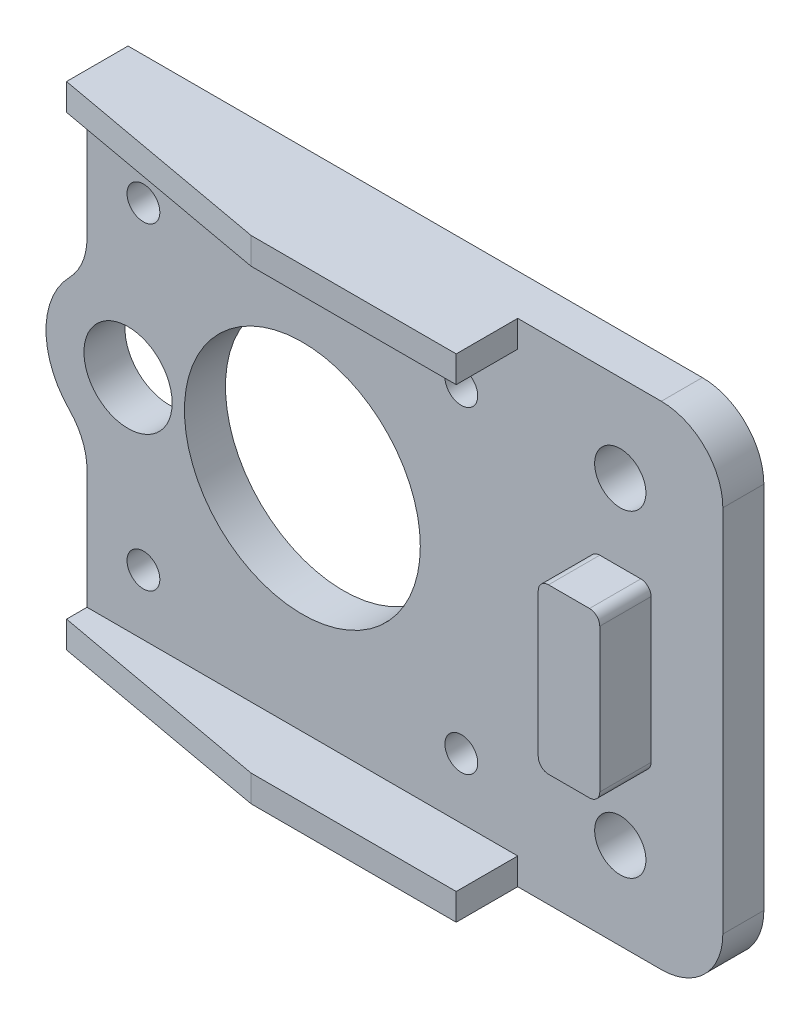
SolidWorks part; units mm, degrees
ref_plane "前视基准面" through (0, 0, 0) normal (0, 0, 1) x (1, 0, 0)
ref_plane "上视基准面" through (0, 0, 0) normal (0, 1, 0) x (1, 0, 0)
ref_plane "右视基准面" through (0, 0, 0) normal (1, 0, 0) x (0, 0, -1)
sketch "草图1" plane through (0, 0, 0) normal (0, 0, 1) x (1, 0, 0)
  line L0 (-21, 6.9282) -> (-21, 24) construction
  line L1 (-21, -24) -> (21, -24) construction
  line L2 (-21, -24) -> (-21, -6.9282) construction
  line L3 (-21, 24) -> (21, 24) construction
  line L4 (21, -24) -> (21, 24) construction
  line L5 (-21, -24) -> (21, 24) construction
  line L6 (-21, 24) -> (21, -24) construction
  line L7 (-21, 24) -> (35, 24)
  line L8 (-21, 24) -> (-21, 9.798)
  line L9 (-21, -24) -> (35, -24)
  line L10 (41, 18) -> (41, -18)
  line L11 (-21, -9.798) -> (-21, -24)
  line L12 (-1000, 0) -> (49000, 0) construction
  circle A0 centre (0, 0) radius 11.5
  circle A1 centre (15.5, 15.5) radius 1.6
  circle A2 centre (15.5, -15.5) radius 1.6
  circle A3 centre (-15.5, -15.5) radius 1.6
  circle A4 centre (-15.5, 15.5) radius 1.6
  circle A5 centre (-17, 0) radius 4.3
  arc A6 (-22.7143, 5.5988) -> (-22.7143, -5.5988) centre (-17, 0) ccw
  arc A7 (35, -24) -> (41, -18) centre (35, -18) ccw
  arc A8 (35, 24) -> (41, 18) centre (35, 18) cw
  arc A9 (-21, -9.798) -> (-22.7143, -5.5988) centre (-27, -9.798) ccw
  arc A10 (-21, 9.798) -> (-22.7143, 5.5988) centre (-27, 9.798) cw
  circle A11 centre (31, 15.5) radius 2.5
  circle A12 centre (31, -15.5) radius 2.5
  point P0 (0, 0)
  point P21 (0, 0)
  dimension "D4" = 23
  dimension "D7" = 3.2
  dimension "D9" = 8.6
  dimension "D11" = 8
  dimension "D12" = 6
  dimension "D13" = 5
  dimension "D1" = 48
  dimension "D2" = 42
  dimension "D3" = 20
  dimension "D5" = 15.5
  dimension "D6" = 15.5
  dimension "D10" = 17
  dimension "D14" = 31
  dimension "D8" = 4
extrude "凸台-拉伸3" add sketch "草图1" along normal blind 4
sketch "草图4" plane through (0, 0, 4) normal (0, 0, 1) x (1, 0, 0)
  line L0 (-1000, 0) -> (49000, 0) construction
  line L1 (-21, 24) -> (21, 24)
  line L2 (-21, 24) -> (-21, 21.4)
  line L3 (-21, 21.4) -> (21, 21.4)
  line L4 (21, 24) -> (21, 21.4)
  line L5 (29, 8) -> (33, 8)
  line L6 (28, 7) -> (28, -7)
  line L7 (29, -8) -> (33, -8)
  line L8 (34, 7) -> (34, -7)
  line L9 (21, -24) -> (21, -21.4)
  line L10 (-21, -21.4) -> (21, -21.4)
  line L11 (-21, -24) -> (-21, -21.4)
  line L12 (-21, -24) -> (21, -24)
  arc A0 (28, -7) -> (29, -8) centre (29, -7) ccw
  arc A1 (33, -8) -> (34, -7) centre (33, -7) ccw
  arc A2 (29, 8) -> (28, 7) centre (29, 7) ccw
  arc A3 (33, 8) -> (34, 7) centre (33, 7) cw
  point P20 (34, -8)
  point P23 (28, 8)
  point P26 (34, 8)
  line M10 (35, 24) -> (-21, 24)
  line M11 (-21, 24) -> (-21, 9.798)
  dimension "D6" = 1
  dimension "D1" = 6
  dimension "D2" = 28
  dimension "D3" = 16
  dimension "D4" = 2.6
  dimension "D5" = 21
  dimension "D7" = 42.8
extrude "凸台-拉伸4" add sketch "草图4" along normal blind 6 contours L4 L3 M10 M11 | L12 L9 L10 L11 region at (0, 22.7, 4)
extrude "凸台-拉伸5" add sketch "草图4<3>" along normal blind 5 contours L6 L0 L8 L5 | L0 L6 L7 L8 region at (31, 3.9659, 4) region at (31, -3.9659, 4)
sketch "草图4<3>" plane through (0, 0, 4) normal (0, 0, 1) x (1, 0, 0) same geometry as "草图4"
chamfer "倒角3" distance 4 distance2 22 1 edges at (-21, 22.7, 10) first distance on face at (-21, 19.3662, 5.1667)
chamfer "倒角4" distance 22 distance2 4 1 edges at (-21, -22.7, 10) first distance on face at (0, -22.7, 10)
chamfer "倒角2" [suppressed] distance 5 angle 45
